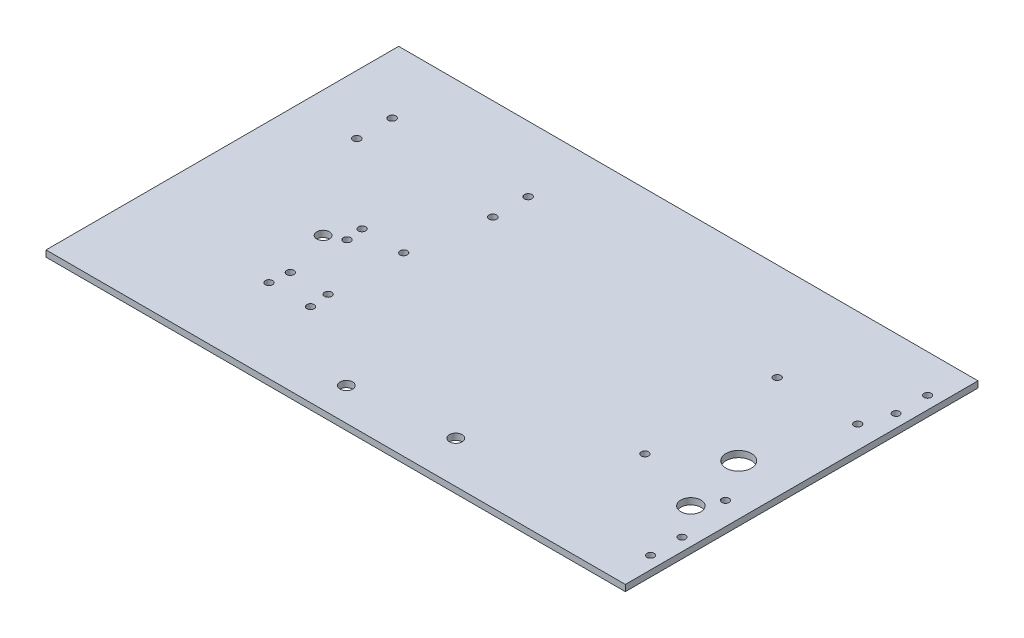
SolidWorks part; units mm, degrees
ref_plane "Front Plane" through (0, 0, 0) normal (0, 0, 1) x (1, 0, 0)
ref_plane "Top Plane" through (0, 0, 0) normal (0, 1, 0) x (1, 0, 0)
ref_plane "Right Plane" through (0, 0, 0) normal (1, 0, 0) x (0, 0, -1)
sketch "Sketch1" plane through (0, 0, 0) normal (0, 1, 0) x (1, 0, 0)
  line L1 (-158.75, 88.9) -> (158.75, 88.9)
  line L2 (-158.75, 88.9) -> (-158.75, -88.9)
  line L3 (-158.75, -88.9) -> (158.75, -88.9)
  line L4 (158.75, 88.9) -> (158.75, -88.9)
  line L5 (-158.75, 88.9) -> (158.75, -88.9) construction
  line L6 (-158.75, -88.9) -> (158.75, 88.9) construction
  circle A0 centre (-95.25, -12.7) radius 3.175
  circle A1 centre (107.95, -6.35) radius 6.4135
  circle A4 centre (-129.032, 55.88) radius 1.905
  circle A5 centre (-60.452, 55.88) radius 1.905
  circle A7 centre (-129.032, 38.1) radius 1.905
  circle A8 centre (-60.452, 38.1) radius 1.905
  point P0 (0, 0)
  dimension "D3" = 6.35
  dimension "D4" = 12.827
  dimension "D14" = 3.81
  dimension "D17" = 17.78
  dimension "D1" = 317.5
  dimension "D2" = 177.8
  dimension "D5" = 63.5
  dimension "D6" = 266.7
  dimension "D7" = 95.25
  dimension "D8" = 76.2
  dimension "D13" = 29.718
  dimension "D15" = 68.58
  dimension "D16" = 127
extrude "Boss-Extrude1" add sketch "Sketch1" along normal blind 3.175
sketch "Sketch2" plane through (0, 3.175, 0) normal (0, 1, 0) x (1, 0, 0)
  line L0 (-158.75, 88.9) -> (-158.75, -88.9) construction
  line L1 (-158.75, -88.9) -> (158.75, -88.9) construction
  circle A0 centre (-89.0817, -33.177) radius 1.905
  circle A1 centre (-132.1376, -36.4483) radius 1.905
  dimension "D1" = 3.81
  dimension "D2" = 69.6683
  dimension "D3" = 52.4517
  dimension "D4" = 55.723
  dimension "D5" = 43.18
extrude "Cut-Extrude1" [suppressed] cut sketch "Sketch2" against normal through all
sketch "Sketch3" plane through (0, 0, 0) normal (0, -1, 0) x (-1, 0, 0)
  line L0 (158.75, -88.9) -> (-158.75, -88.9) construction
  line L1 (158.75, 88.9) -> (158.75, -88.9) construction
  circle A0 centre (23.8295, -72.39) radius 3.175
  circle A1 centre (-26.7643, -67.818) radius 3.175
  dimension "D1" = 6.35
  dimension "D2" = 4.572
  dimension "D3" = 16.51
  dimension "D4" = 185.5143
  dimension "D5" = 50.8
extrude "Cut-Extrude2" cut sketch "Sketch3" against normal through all
sketch "Sketch4" plane through (0, 3.175, 0) normal (0, 1, 0) x (1, 0, 0)
  line L0 (-158.75, -88.9) -> (158.75, -88.9) construction
  line L1 (158.75, 88.9) -> (133.35, 88.9)
  line L2 (158.75, 88.9) -> (158.75, -88.9)
  line L3 (158.75, -88.9) -> (133.35, -88.9)
  line L4 (133.35, 88.9) -> (133.35, -88.9)
  dimension "D1" = 25.4
extrude "Cut-Extrude3" cut sketch "Sketch4" against normal through all
sketch "Sketch5" plane through (0, 3.175, 0) normal (0, 1, 0) x (1, 0, 0)
  line L0 (133.35, 88.9) -> (-158.75, 88.9) construction
  line L1 (133.35, 88.9) -> (133.35, -88.9) construction
  circle A0 centre (115.57, -38.1) radius 5.08
  dimension "D3" = 10.16
  dimension "D1" = 127
  dimension "D2" = 17.78
extrude "Cut-Extrude4" cut sketch "Sketch5" against normal through all
sketch "Sketch6" plane through (0, 0, 0) normal (0, -1, 0) x (1, 0, 0)
  line L0 (-158.75, 88.9) -> (133.35, 88.9) construction
  line L1 (133.35, -88.9) -> (133.35, 88.9) construction
  line L2 (133.35, -88.9) -> (-158.75, -88.9) construction
  circle A0 centre (127, 69.85) radius 1.8034
  circle A2 centre (127, 53.975) radius 1.8034
  circle A3 centre (127, -53.975) radius 1.8034
  circle A4 centre (127, -69.85) radius 1.8034
  dimension "D4" = 3.6068
  dimension "D5" = 6.35
  dimension "D1" = 15.875
  dimension "D2" = 19.05
  dimension "D3" = 6.35
  dimension "D6" = 15.875
  dimension "D7" = 19.05
extrude "Cut-Extrude5" cut sketch "Sketch6" against normal through all
sketch "Sketch7" plane through (0, 3.175, 0) normal (0, 1, 0) x (1, 0, 0)
  line L0 (133.35, 88.9) -> (133.35, -88.9) construction
  line L1 (133.35, 88.9) -> (-158.75, 88.9) construction
  line L2 (-158.75, 88.9) -> (-158.75, -88.9) construction
  circle A1 centre (121.92, 39.6875) radius 1.8415
  circle A2 centre (81.28, 39.6875) radius 1.8415
  circle A3 centre (81.28, -26.9875) radius 1.8415
  circle A4 centre (121.92, -26.9875) radius 1.8415
  circle A5 centre (-88.265, -46.99) radius 1.8415
  circle A6 centre (-67.31, -46.99) radius 1.8415
  circle A7 centre (-87.3125, -37.1475) radius 1.8415
  circle A8 centre (-68.2625, -37.1475) radius 1.8415
  circle A9 centre (-87.3125, -8.5725) radius 1.8415
  circle A10 centre (-88.265, 0) radius 1.8415
  circle A11 centre (-67.31, 0) radius 1.8415
  dimension "D1" = 11.43
  dimension "D5" = 3.683
  dimension "D10" = 3.683
  dimension "D15" = 3.683
  dimension "D2" = 40.64
  dimension "D3" = 66.675
  dimension "D4" = 49.2125
  dimension "D6" = 70.485
  dimension "D7" = 20.955
  dimension "D8" = 71.4375
  dimension "D9" = 19.05
  dimension "D11" = 88.9
  dimension "D12" = 8.5725
  dimension "D13" = 28.575
  dimension "D14" = 9.8425
extrude "Cut-Extrude6" cut sketch "Sketch7" against normal through all
